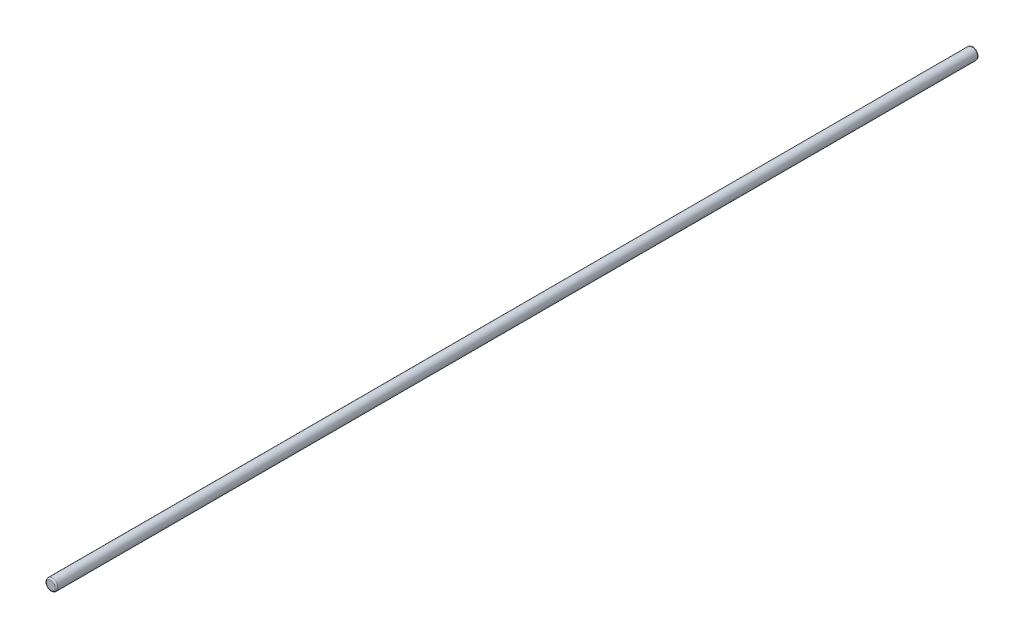
SolidWorks part; units mm, degrees
ref_plane "Front Plane" through (0, 0, 0) normal (0, 0, 1) x (1, 0, 0)
ref_plane "Top Plane" through (0, 0, 0) normal (0, 1, 0) x (1, 0, 0)
ref_plane "Right Plane" through (0, 0, 0) normal (1, 0, 0) x (0, 0, -1)
sketch "Sketch1" plane through (0, 0, 0) normal (0, 0, 1) x (1, 0, 0)
  circle A0 centre (0, 0) radius 4
extrude "Extrude2" add sketch "Sketch1" along normal blind 323.625 and the other way blind 323.625
cosmetic thread "Cosmetic Thread2" parameters "D2"=7
fillet "Fillet2" radius 1 1 edges at (4, 0, -323.625)
fillet "Fillet3" radius 1 1 edges at (4, 0, 323.625)
